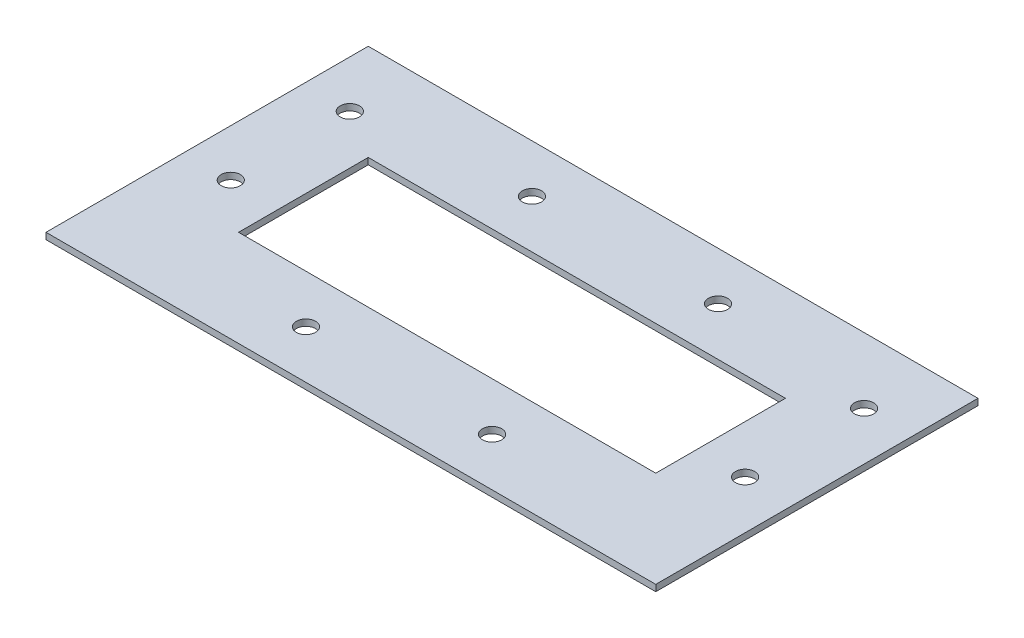
SolidWorks part; units mm, degrees
ref_plane "Front" through (0, 0, 0) normal (0, 0, 1) x (1, 0, 0)
ref_plane "Top" through (0, 0, 0) normal (0, 1, 0) x (1, 0, 0)
ref_plane "Right" through (0, 0, 0) normal (1, 0, 0) x (0, 0, -1)
sketch "Sketch2" plane through (0, 0, 0) normal (0, 1, 0) x (1, 0, 0)
  line L0 (-32.5, 25.1025) -> (-32.5, 10.1025) construction
  line L1 (-47.5, -25.1025) -> (47.5, -25.1025)
  line L2 (-47.5, -25.1025) -> (-47.5, 25.1025)
  line L3 (-47.5, 25.1025) -> (47.5, 25.1025)
  line L4 (47.5, -25.1025) -> (47.5, 25.1025)
  line L5 (-47.5, -25.1025) -> (47.5, 25.1025) construction
  line L6 (-47.5, 25.1025) -> (47.5, -25.1025) construction
  line L7 (-32.5, -10.1025) -> (32.5, -10.1025)
  line L8 (-32.5, -10.1025) -> (-32.5, 10.1025)
  line L9 (-32.5, 10.1025) -> (32.5, 10.1025)
  line L10 (32.5, -10.1025) -> (32.5, 10.1025)
  line L11 (-32.5, -10.1025) -> (32.5, 10.1025) construction
  line L12 (-32.5, 10.1025) -> (32.5, -10.1025) construction
  line L13 (32.5, 10.1025) -> (32.5, 25.1025) construction
  line L14 (-32.5, 17.6025) -> (32.5, 17.6025) construction
  line L15 (32.5, 10.1025) -> (47.5, 10.1025) construction
  line L16 (32.5, -10.1025) -> (47.5, -10.1025) construction
  line L17 (39.9789, 25.1025) -> (39.9789, -25.1025) construction
  line L18 (-47.5, 10.1025) -> (-32.5, 10.1025) construction
  line L19 (-47.5, -10.1025) -> (-32.5, -10.1025) construction
  line L20 (-32.5, -10.1025) -> (-32.5, -25.1025) construction
  line L21 (32.5, -10.1025) -> (32.5, -25.1025) construction
  line L22 (-40.149, 25.1025) -> (-40.149, -25.1025) construction
  line L23 (-32.5, -17.6025) -> (32.5, -17.6025) construction
  circle A0 centre (-14.5, 17.6025) radius 1.5
  circle A1 centre (14.5, 17.6025) radius 1.5
  circle A2 centre (-40.149, 14.8779) radius 1.5
  circle A3 centre (-40.149, -3.6665) radius 1.5
  circle A4 centre (39.9789, 14.8779) radius 1.5
  circle A5 centre (39.9789, -3.6665) radius 1.5
  circle A6 centre (-14.5, -17.6025) radius 1.5
  circle A7 centre (14.5, -17.6025) radius 1.5
  point P0 (0, 0)
  point P6 (0, 0)
  point P35 (12.5846, -17.7663)
  point P38 (0, 0)
  point P41 (32.5, 17.6025)
  point P44 (-32.5, 17.6025)
  point P45 (-32.5, 17.6025)
  point P48 (-32.5, 17.6025)
  point P49 (32.5, 17.6025)
  point P50 (-40.149, -3.6665)
  point P51 (12.5846, 17.6025)
  point P52 (-13.7161, 17.6025)
  point P53 (-14.5, -17.6025)
  point P54 (14.5, -17.6025)
  point P55 (39.9789, 14.8779)
  point P56 (39.9789, -3.6665)
  dimension "D7" = 18
  dimension "D8" = 18
  dimension "D1" = 50.205
  dimension "D2" = 15
  dimension "D3" = 15
  dimension "D4" = 15
  dimension "D5" = 15
  dimension "D6" = 95
extrude "Boss-Extrude2" add sketch "Sketch2" along normal blind 1
